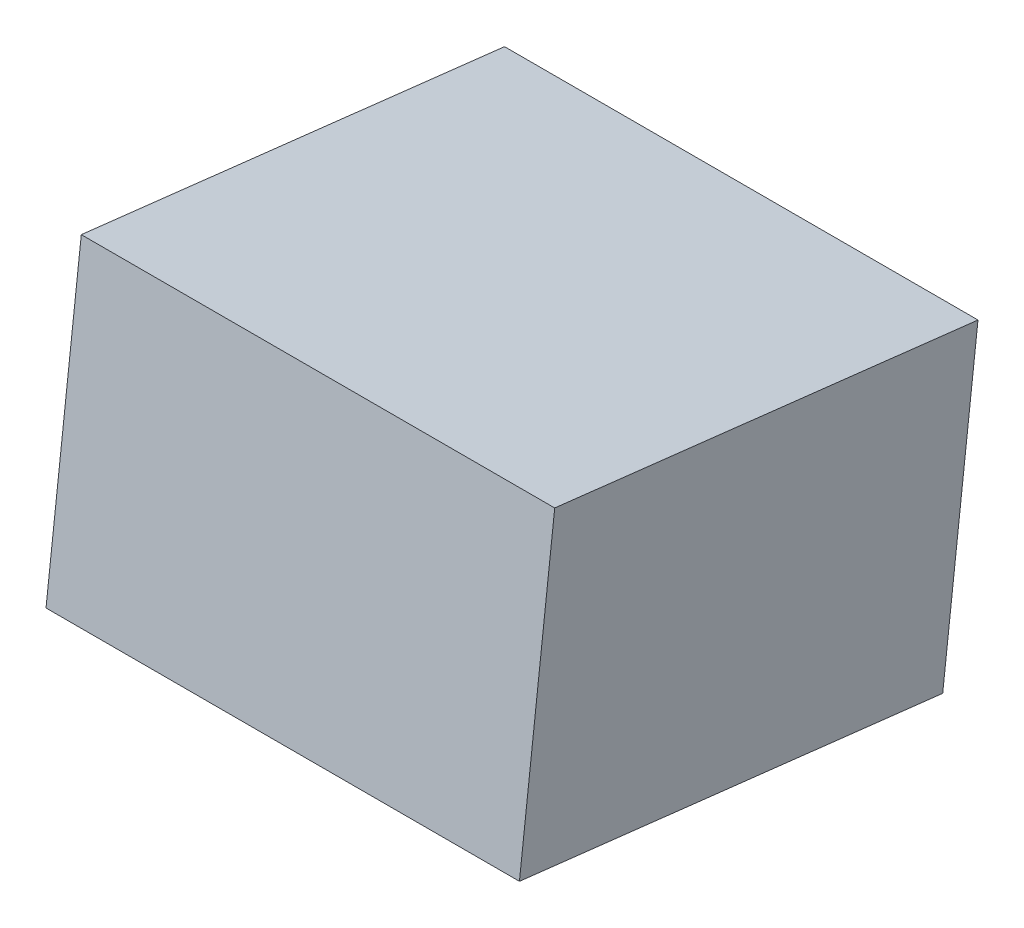
SolidWorks part; units mm, degrees
ref_plane "Front Plane" through (0, 0, 0) normal (0, 0, 1) x (1, 0, 0)
ref_plane "Top Plane" through (0, 0, 0) normal (0, 1, 0) x (1, 0, 0)
ref_plane "Right Plane" through (0, 0, 0) normal (1, 0, 0) x (0, 0, -1)
sketch "Sketch1" plane through (0, 343.9788, -39.7026) normal (0, 0.9934, -0.1147) x (1, 0, 0)
  line L1 (-247.0345, 875.5294) -> (-47.0345, 875.5294)
  line L2 (-247.0345, 875.5294) -> (-247.0345, 1055.5294)
  line L3 (-247.0345, 1055.5294) -> (-47.0345, 1055.5294)
  line L4 (-47.0345, 875.5294) -> (-47.0345, 1055.5294)
  line L5 (-247.0345, 875.5294) -> (-47.0345, 1055.5294) construction
  line L6 (-247.0345, 1055.5294) -> (-47.0345, 875.5294) construction
  point P0 (-147.0345, 965.5294)
  point P6 (0, 0)
  point P7 (116.038, 943.0457)
  point P8 (-147.0345, 965.5294)
  dimension "D1" = 180
  dimension "D2" = 200
extrude "Boss-Extrude1" add sketch "Sketch1" along normal blind 130
